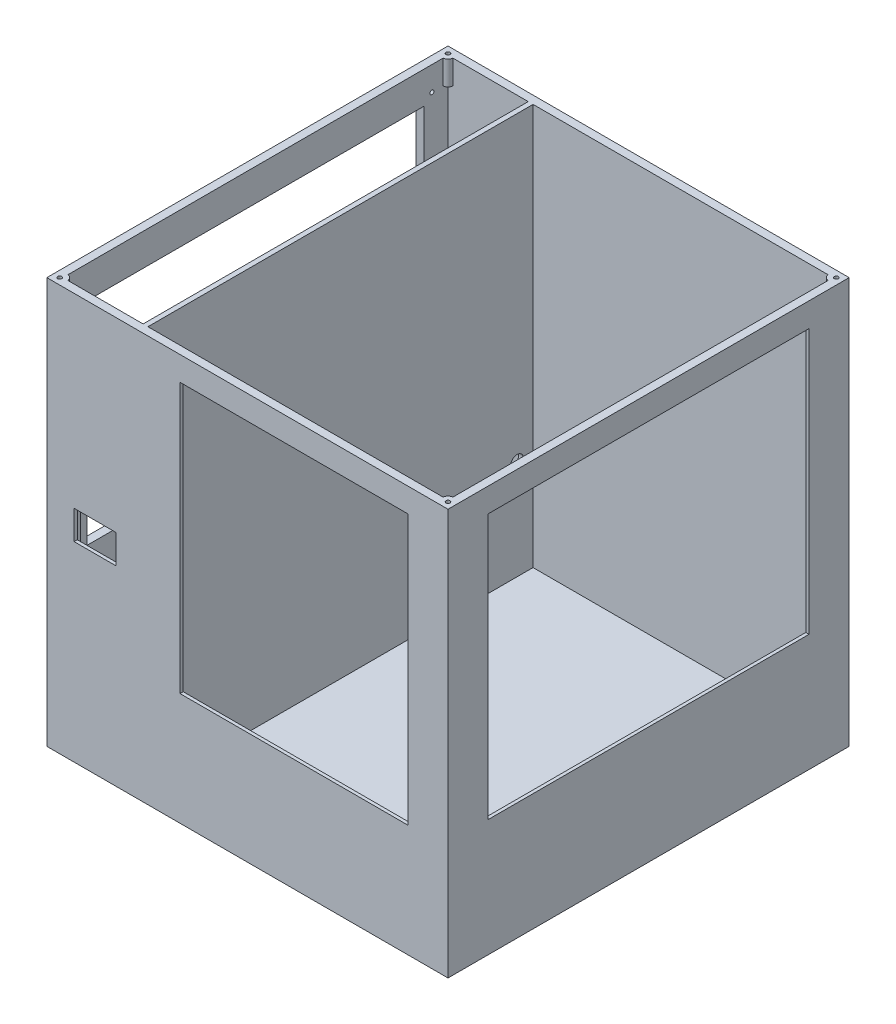
SolidWorks part; units mm, degrees
ref_plane "Спереди" through (0, 0, 0) normal (0, 0, 1) x (1, 0, 0)
ref_plane "Сверху" through (0, 0, 0) normal (0, 1, 0) x (1, 0, 0)
ref_plane "Справа" through (0, 0, 0) normal (1, 0, 0) x (0, 0, -1)
sketch "Эскиз1" plane through (0, 0, 0) normal (0, 1, 0) x (1, 0, 0)
  line L1 (-125, -125) -> (125, -125)
  line L2 (-125, -125) -> (-125, 125)
  line L3 (-125, 125) -> (125, 125)
  line L4 (125, -125) -> (125, 125)
  line L5 (-125, -125) -> (125, 125) construction
  line L6 (-125, 125) -> (125, -125) construction
  point P0 (0, 0)
  dimension "D1" = 250
  dimension "D2" = 250
extrude "Бобышка-Вытянуть1" add sketch "Эскиз1" along normal blind 3
sketch "Эскиз2" plane through (0, 3, 0) normal (0, 1, 0) x (1, 0, 0)
  line L1 (-125, -125) -> (125, -125)
  line L2 (-125, -125) -> (-125, 125)
  line L3 (-125, 125) -> (125, 125)
  line L4 (125, -125) -> (125, 125)
  line L5 (-125, -125) -> (125, 125) construction
  line L6 (-125, 125) -> (125, -125) construction
  line L7 (-120, -120) -> (120, -120)
  line L8 (-120, -120) -> (-120, 120)
  line L9 (-120, 120) -> (120, 120)
  line L10 (120, -120) -> (120, 120)
  line L11 (-120, -120) -> (120, 120) construction
  line L12 (-120, 120) -> (120, -120) construction
  point P0 (0, 0)
  point P6 (0, 0)
  dimension "D1" = 250
  dimension "D2" = 250
  dimension "D3" = 240
  dimension "D4" = 240
extrude "Бобышка-Вытянуть2" add sketch "Эскиз2" along normal blind 250
sketch "Эскиз3" plane through (0, 3, 0) normal (0, 1, 0) x (1, 0, 0)
  line L0 (120, 120) -> (-120, 120) construction
  line L1 (-70, 120) -> (-67, 120)
  line L2 (-70, 120) -> (-70, -120)
  line L3 (-70, -120) -> (-67, -120)
  line L4 (-67, 120) -> (-67, -120)
  line L5 (-120, -120) -> (120, -120) construction
  line L6 (-120, 120) -> (-120, -120) construction
  dimension "D1" = 3
  dimension "D2" = 50
extrude "Бобышка-Вытянуть3" add sketch "Эскиз3" along normal blind 250
sketch "Эскиз8" plane through (125, 0, 0) normal (1, 0, 0) x (0, 0, -1)
  line L0 (-125, 3) -> (125, 3) construction
  line L1 (-100, 73) -> (100, 73)
  line L2 (-100, 73) -> (-100, 238)
  line L3 (-100, 238) -> (100, 238)
  line L4 (100, 73) -> (100, 238)
  line L5 (-100, 73) -> (100, 238) construction
  line L6 (-100, 238) -> (100, 73) construction
  line L7 (-125, 253) -> (125, 253) construction
  line L8 (125, 253) -> (125, 0) construction
  point P0 (0, 155.5)
  dimension "D1" = 70
  dimension "D2" = 15
  dimension "D3" = 25
extrude "Вырез-Вытянуть4" cut sketch "Эскиз8" against normal blind 8
sketch "Эскиз9" plane through (120, 0, 0) normal (-1, 0, 0) x (0, 0, 1)
  line L0 (100, 73) -> (100, 238) construction
  line L1 (-110, 63) -> (110, 63)
  line L2 (-110, 63) -> (-110, 248)
  line L3 (-110, 248) -> (110, 248)
  line L4 (110, 63) -> (110, 248)
  line L5 (-110, 63) -> (110, 248) construction
  line L6 (-110, 248) -> (110, 63) construction
  line L7 (100, 238) -> (-100, 238) construction
  point P0 (0, 155.5)
  dimension "D1" = 10
  dimension "D2" = 10
extrude "Вырез-Вытянуть5" cut sketch "Эскиз9" against normal blind 3
sketch "Эскиз11" plane through (0, 0, 125) normal (0, 0, 1) x (1, 0, 0)
  line L0 (125, 253) -> (125, 0) construction
  line L1 (-42, 238) -> (100, 238)
  line L2 (-42, 238) -> (-42, 70)
  line L3 (-42, 70) -> (100, 70)
  line L4 (100, 238) -> (100, 70)
  line L5 (-125, 0) -> (125, 0) construction
  line L6 (-125, 253) -> (125, 253) construction
  line L7 (-125, 253) -> (-125, 0) construction
  dimension "D1" = 25
  dimension "D2" = 70
  dimension "D3" = 15
  dimension "D4" = 83
extrude "Вырез-Вытянуть6" cut sketch "Эскиз11" against normal blind 10
sketch "Эскиз12" plane through (0, 0, 120) normal (0, 0, -1) x (-1, 0, 0)
  line L0 (42, 238) -> (-100, 238) construction
  line L1 (-110, 248) -> (52, 248)
  line L2 (-110, 248) -> (-110, 60)
  line L3 (-110, 60) -> (52, 60)
  line L4 (52, 248) -> (52, 60)
  line L5 (42, 238) -> (42, 70) construction
  line L6 (-100, 238) -> (-100, 70) construction
  line L7 (42, 70) -> (-100, 70) construction
  dimension "D1" = 10
  dimension "D2" = 10
  dimension "D3" = 10
  dimension "D4" = 10
extrude "Вырез-Вытянуть7" cut sketch "Эскиз12" against normal blind 3
sketch "Эскиз16" plane through (0, 0, 125) normal (0, 0, 1) x (1, 0, 0)
  line L0 (-125, 253) -> (-125, 0) construction
  line L1 (-108, 119) -> (-82, 119)
  line L2 (-108, 119) -> (-108, 137)
  line L3 (-108, 137) -> (-82, 137)
  line L4 (-82, 119) -> (-82, 137)
  line L5 (-108, 119) -> (-82, 137) construction
  line L6 (-108, 137) -> (-82, 119) construction
  line L8 (-125, 0) -> (125, 0) construction
  point P0 (-95, 128)
  dimension "D1" = 26
  dimension "D2" = 18
  dimension "D3" = 30
  dimension "D4" = 128
extrude "Вырез-Вытянуть10" cut sketch "Эскиз16" against normal blind 5
sketch "Эскиз17" plane through (-125, 0, 0) normal (-1, 0, 0) x (0, 0, 1)
  line L0 (-125, 0) -> (125, 0) construction
  line L1 (101, 86) -> (110, 86)
  line L2 (101, 86) -> (101, 75)
  line L3 (101, 75) -> (110, 75)
  line L4 (110, 86) -> (110, 75)
  line L5 (66, 83) -> (81, 83)
  line L6 (66, 83) -> (66, 75)
  line L7 (66, 75) -> (81, 75)
  line L8 (81, 83) -> (81, 75)
  line L9 (125, 253) -> (125, 0) construction
  dimension "D1" = 11
  dimension "D2" = 9
  dimension "D3" = 8
  dimension "D4" = 15
  dimension "D5" = 75
  dimension "D6" = 75
  dimension "D7" = 20
  dimension "D8" = 15
extrude "Вырез-Вытянуть11" cut sketch "Эскиз17" against normal blind 10
sketch "Эскиз21" plane through (0, 0, 120) normal (0, 0, -1) x (-1, 0, 0)
  line L1 (81, 114) -> (109, 114)
  line L2 (81, 114) -> (81, 142)
  line L3 (81, 142) -> (109, 142)
  line L4 (109, 114) -> (109, 142)
  line L5 (81, 114) -> (109, 142) construction
  line L6 (81, 142) -> (109, 114) construction
  point P0 (95, 128)
  dimension "D1" = 28
  dimension "D2" = 28
extrude "Вырез-Вытянуть14" cut sketch "Эскиз21" against normal blind 3
sketch "Эскиз22" plane through (0, 0, -120) normal (0, 0, 1) x (1, 0, 0)
  line L0 (-120, 253) -> (-120, 3) construction
  line L5 (-120, 73) -> (-70, 73)
  line L6 (-120, 73) -> (-120, 70)
  line L7 (-120, 70) -> (-70, 70)
  line L8 (-70, 73) -> (-70, 70)
  line L9 (-70, 253) -> (-70, 3) construction
  line L10 (-70, 3) -> (-120, 3) construction
  dimension "D1" = 3
  dimension "D2" = 67
extrude "Бобышка-Вытянуть4" add sketch "Эскиз22" along normal blind 240
sketch "Эскиз24" plane through (-67, 0, 0) normal (1, 0, 0) x (0, 0, -1)
  line L0 (-120, 3) -> (120, 3) construction
  line L1 (120, 253) -> (120, 3) construction
  circle A0 centre (110, 65) radius 4
  dimension "D1" = 8
  dimension "D2" = 62
  dimension "D3" = 10
extrude "Вырез-Вытянуть15" cut sketch "Эскиз24" against normal blind 10
sketch "Эскиз25" plane through (-125, 0, 0) normal (-1, 0, 0) x (0, 0, 1)
  line L0 (-125, 253) -> (125, 253) construction
  line L1 (-105, 233) -> (105, 233)
  line L2 (-105, 233) -> (-105, 101)
  line L3 (-105, 101) -> (105, 101)
  line L4 (105, 233) -> (105, 101)
  line L5 (125, 253) -> (125, 0) construction
  line L6 (-125, 253) -> (-125, 0) construction
  line L7 (110, 86) -> (101, 86) construction
  dimension "D1" = 20
  dimension "D2" = 20
  dimension "D3" = 20
  dimension "D4" = 15
extrude "Вырез-Вытянуть16" cut sketch "Эскиз25" against normal blind 10
sketch "Эскиз26" plane through (-125, 0, 0) normal (-1, 0, 0) x (0, 0, 1)
  line L0 (-105, 101) -> (105, 101) construction
  line L1 (-105, 233) -> (-105, 101) construction
  line L2 (105, 101) -> (105, 233) construction
  line L3 (105, 233) -> (-105, 233) construction
  circle A0 centre (-110, 238) radius 1.25
  circle A1 centre (110, 238) radius 1.25
  circle A2 centre (110, 96) radius 1.25
  circle A3 centre (-110, 96) radius 1.25
  dimension "D1" = 2.5
  dimension "D2" = 2.5
  dimension "D3" = 2.5
  dimension "D4" = 2.5
  dimension "D5" = 5
  dimension "D6" = 5
  dimension "D7" = 5
  dimension "D8" = 5
  dimension "D9" = 5
  dimension "D10" = 5
  dimension "D11" = 5
  dimension "D12" = 5
extrude "Вырез-Вытянуть17" cut sketch "Эскиз26" against normal blind 10
sketch "Эскиз27" plane through (0, 73, 0) normal (0, 1, 0) x (1, 0, 0)
  line L0 (-120, 120) -> (-120, -120) construction
  line L1 (-70, 120) -> (-120, 120) construction
  circle A0 centre (-95, 10) radius 5
  dimension "D2" = 10
  dimension "D1" = 25
  dimension "D3" = 110
extrude "Вырез-Вытянуть18" cut sketch "Эскиз27" against normal blind 10
sketch "Эскиз29" plane through (0, 73, 0) normal (0, 1, 0) x (1, 0, 0)
  line L0 (-120, 120) -> (-120, -120) construction
  line L1 (-112.5, 100) -> (-77.5, 100)
  line L2 (-112.5, 100) -> (-112.5, 30)
  line L3 (-112.5, 30) -> (-77.5, 30)
  line L4 (-77.5, 100) -> (-77.5, 30)
  line L6 (-70, 120) -> (-120, 120) construction
  dimension "D1" = 70
  dimension "D2" = 35
  dimension "D3" = 7.5
  dimension "D4" = 20
extrude "Вырез-Вытянуть19" cut sketch "Эскиз29" against normal blind 10
sketch "Эскиз30" plane through (0, 73, 0) normal (0, 1, 0) x (1, 0, 0)
  line L0 (-77.5, 100) -> (-112.5, 100) construction
  line L1 (-120, 120) -> (-120, -120) construction
  line L2 (-70, -120) -> (-70, 120) construction
  line L3 (-112.5, 30) -> (-77.5, 30) construction
  line L4 (-70, 120) -> (-70, -120) construction
  circle A0 centre (-75, 105) radius 1.25
  circle A1 centre (-115, 105) radius 1.25
  circle A2 centre (-115, 25) radius 1.25
  circle A3 centre (-75, 25) radius 1.25
  dimension "D1" = 2.5
  dimension "D2" = 2.5
  dimension "D7" = 2.5
  dimension "D8" = 2.5
  dimension "D3" = 5
  dimension "D4" = 5
  dimension "D5" = 5
  dimension "D6" = 5
  dimension "D9" = 5
  dimension "D10" = 5
  dimension "D11" = 5
  dimension "D12" = 5
extrude "Вырез-Вытянуть20" cut sketch "Эскиз30" against normal blind 3
sketch "Эскиз31" plane through (0, 0, -120) normal (0, 0, 1) x (1, 0, 0)
  line L1 (120, 253) -> (117, 253)
  line L2 (120, 253) -> (120, 238)
  line L3 (120, 238) -> (117, 238)
  line L4 (117, 253) -> (117, 238)
  line L5 (-120, 253) -> (-117, 253)
  line L6 (-120, 253) -> (-120, 238)
  line L7 (-120, 238) -> (-117, 238)
  line L8 (-117, 253) -> (-117, 238)
  point P5 (118.5, 238)
  dimension "D1" = 15
  dimension "D2" = 3
  dimension "D3" = 15
  dimension "D4" = 3
extrude "Бобышка-Вытянуть5" add sketch "Эскиз31" along normal blind 3
sketch "Эскиз32" plane through (0, 0, 120) normal (0, 0, -1) x (-1, 0, 0)
  line L1 (-120, 253) -> (-117, 253)
  line L2 (-120, 253) -> (-120, 238)
  line L3 (-120, 238) -> (-117, 238)
  line L4 (-117, 253) -> (-117, 238)
  line L5 (120, 253) -> (117, 253)
  line L6 (120, 253) -> (120, 238)
  line L7 (120, 238) -> (117, 238)
  line L8 (117, 253) -> (117, 238)
  dimension "D1" = 15
  dimension "D2" = 3
  dimension "D3" = 3
  dimension "D4" = 15
extrude "Бобышка-Вытянуть6" add sketch "Эскиз32" along normal blind 3
sketch "Эскиз33" plane through (0, 253, 0) normal (0, 1, 0) x (1, 0, 0)
  line L0 (-125, -125) -> (125, -125) construction
  line L1 (-125, 125) -> (-125, -125) construction
  line L3 (125, -125) -> (125, 125) construction
  line L4 (125, 125) -> (-125, 125) construction
  circle A0 centre (-121, -121) radius 1.25
  circle A1 centre (-121, 121) radius 1.25
  circle A2 centre (121, 121) radius 1.25
  circle A3 centre (121, -121) radius 1.25
  dimension "D1" = 2.5
  dimension "D4" = 2.5
  dimension "D7" = 2.5
  dimension "D12" = 2.5
  dimension "D2" = 4
  dimension "D3" = 4
  dimension "D5" = 4
  dimension "D6" = 4
  dimension "D8" = 4
  dimension "D9" = 4
  dimension "D10" = 4
  dimension "D11" = 4
extrude "Вырез-Вытянуть21" cut sketch "Эскиз33" against normal blind 7
fillet "Скругление1" radius 3 4 edges at (117, 245.5, -117) (-117, 245.5, -117) (117, 245.5, 117) (-117, 245.5, 117)
